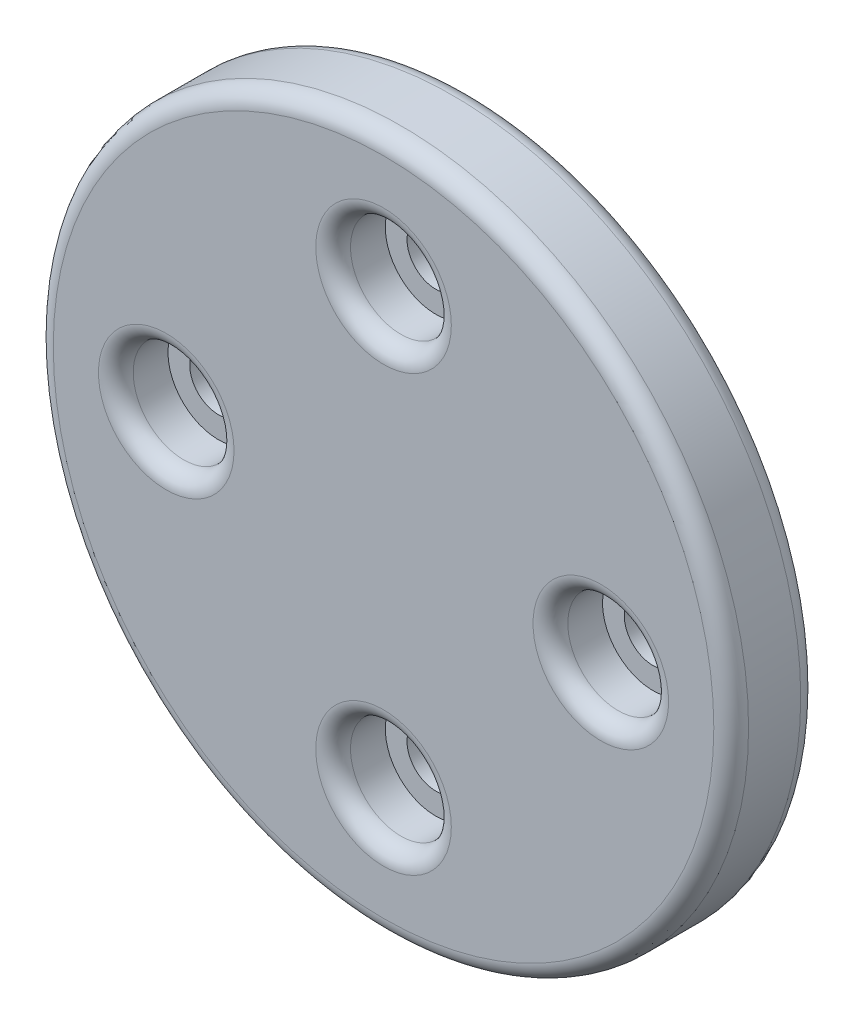
SolidWorks part; units mm, degrees
ref_plane "Ebene vorne" through (0, 0, 0) normal (0, 0, 1) x (1, 0, 0)
ref_plane "Ebene oben" through (0, 0, 0) normal (0, 1, 0) x (1, 0, 0)
ref_plane "Ebene rechts" through (0, 0, 0) normal (1, 0, 0) x (0, 0, -1)
sketch "Skizze1" plane through (0, 0, 0) normal (0, 0, 1) x (1, 0, 0)
  circle A0 centre (0, 0) radius 20
  circle A2 centre (12.5, 0) radius 1.65
  circle A3 centre (0, -12.5) radius 1.65
  circle A4 centre (-12.5, 0) radius 1.65
  circle A5 centre (0, 12.5) radius 1.65
  point P15 (0, 0)
  dimension "D1" = 40
  dimension "D2" = 12.5
  dimension "D3" = 4
  dimension "D4" = 3.3
extrude "Aufsatz-Linear austragen1" add sketch "Skizze1" along normal blind 5 contours A0 | A5 A4 A3 A2 region at (0, 0, 0)
sketch "Skizze2" plane through (0, 0, 5) normal (0, 0, 1) x (1, 0, 0)
  circle A0 centre (0, 12.5) radius 2.9
  circle A1 centre (12.5, 0) radius 2.9
  circle A2 centre (0, -12.5) radius 2.9
  circle A3 centre (-12.5, 0) radius 2.9
  point P12 (0, 0)
  dimension "D1" = 4
  dimension "D2" = 5.8
extrude "Schnitt-Linear austragen1" cut sketch "Skizze2" against normal blind 3
fillet "Verrundung1" radius 1 10 edges at (20, 0, 0) (14.15, 0, 0) (1.65, -12.5, 0) (-10.85, 0, 0) (1.65, 12.5, 0) (20, 0, 5) (-9.6, 0, 5) (2.9, -12.5, 5) (15.4, 0, 5) (2.9, 12.5, 5)
